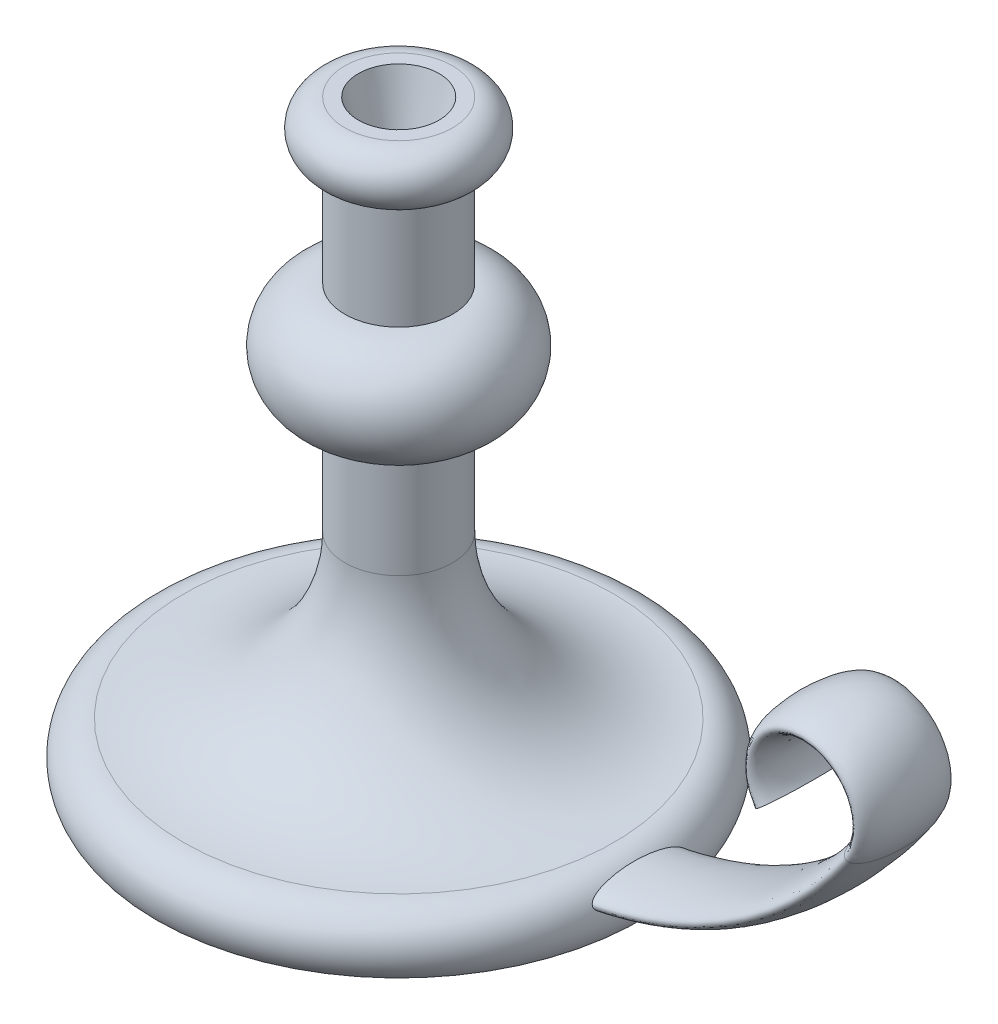
SolidWorks part; units mm, degrees
ref_plane "Front Plane" through (0, 0, 0) normal (0, 0, 1) x (1, 0, 0)
ref_plane "Top Plane" through (0, 0, 0) normal (0, 1, 0) x (1, 0, 0)
ref_plane "Right Plane" through (0, 0, 0) normal (1, 0, 0) x (0, 0, -1)
sketch "Sketch2" plane through (0, 0, 0) normal (0, 0, 1) x (1, 0, 0)
  line L0 (0, 0) -> (0, 220)
  line L1 (0, 220) -> (20, 220)
  line L2 (0, 0) -> (90, 0)
  line L3 (20, 200) -> (20, 160)
  line L4 (20, 120) -> (20, 80)
  arc A0 (20, 220) -> (20, 200) centre (20, 210) cw
  arc A1 (20, 160) -> (20, 120) centre (20, 140) cw
  arc A2 (20, 80) -> (80, 20) centre (80, 80) ccw
  arc A3 (80, 20) -> (90, 0) centre (80, 7.5) cw
  dimension "D4" = 10
  dimension "D5" = 20
  dimension "D7" = 60
  dimension "D8" = 12.5
  dimension "D1" = 20
  dimension "D2" = 220
  dimension "D3" = 90
  dimension "D6" = 40
  dimension "D9" = 80
revolve "Revolve1" add sketch "Sketch2" angle 360 about L0
sketch "Sketch4" plane through (0, 0, 0) normal (0, 0, 1) x (1, 0, 0)
  line L0 (0, 10) -> (60, 10)
  line L1 (0, 227.4356) -> (0, 175.1288) construction
  line L2 (-90, 0) -> (90, 0) construction
  arc A0 (60, 10) -> (183.5921, 75) centre (60, 160) ccw
  arc A1 (183.5921, 75) -> (150.6342, 75) centre (167.1131, 86.3333) ccw
  dimension "D1" = 150
  dimension "D3" = 20
  dimension "D2" = 65
  dimension "D4" = 60
  dimension "D5" = 32.9579
  dimension "D6" = 10
sketch "Sketch5" plane through (0, 0, 0) normal (1, 0, 0) x (0, 0, -1)
  ellipse E0 centre (0, 10) end of major axis (-17.5, 10) minor radius 5
  dimension "D1" = 10
  dimension "D2" = 35
sweep "Sweep1" add profiles "Sketch5" path "Sketch4"
sketch "Sketch6" plane through (0, 220, 0) normal (0, 1, 0) x (1, 0, 0)
  circle A0 centre (0, 0) radius 15
  dimension "D1" = 30
extrude "Cut-Extrude1" cut sketch "Sketch6" against normal blind 25 draft 15
